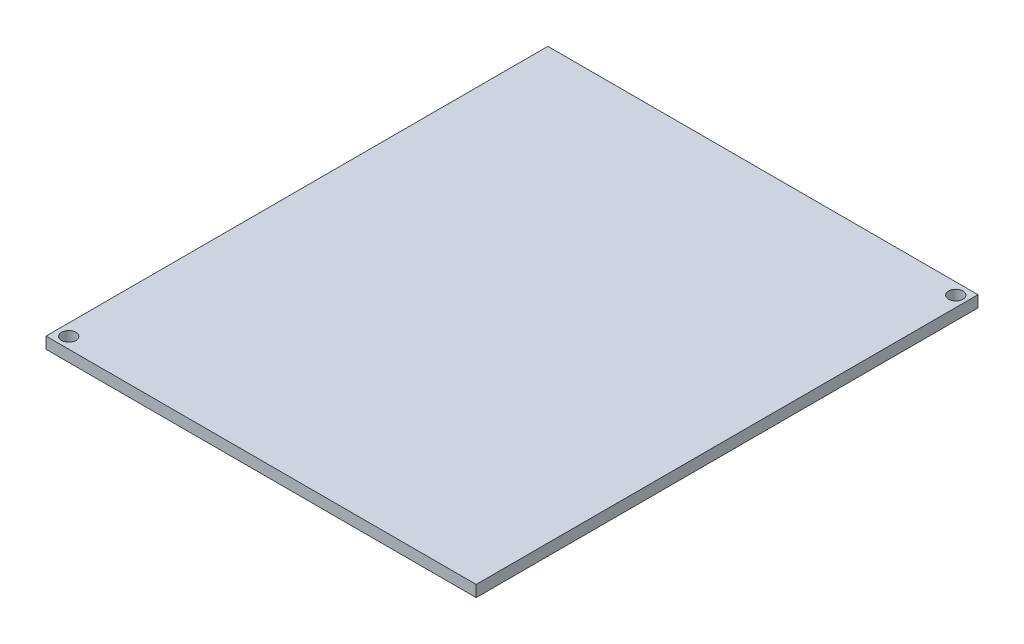
SolidWorks part; units mm, degrees
ref_plane "Přední rovina" through (0, 0, 0) normal (0, 0, 1) x (1, 0, 0)
ref_plane "Horní rovina" through (0, 0, 0) normal (0, 1, 0) x (1, 0, 0)
ref_plane "Pravá rovina" through (0, 0, 0) normal (1, 0, 0) x (0, 0, -1)
sketch "Sketch1" plane through (0, 0, 0) normal (0, 1, 0) x (1, 0, 0)
  line L0 (4105.0112, -3139.6182) -> (4165.0112, -3139.6182) construction
  line L1 (4105.0112, -3138.0182) -> (4165.0112, -3138.0182)
  line L2 (4105.0112, -3138.0182) -> (4105.0112, -3208.0182)
  line L3 (4105.0112, -3208.0182) -> (4165.0112, -3208.0182)
  line L4 (4165.0112, -3138.0182) -> (4165.0112, -3208.0182)
  line L5 (4106.6312, -3138.0182) -> (4106.6312, -3208.0182) construction
  line L6 (4105.0112, -3206.4682) -> (4165.0112, -3206.4682) construction
  line L7 (4163.5112, -3138.0182) -> (4163.5112, -3208.0182) construction
  circle A0 centre (4163.5112, -3139.6182) radius 1
  circle A1 centre (4106.6312, -3206.4682) radius 1
  dimension "D3" = 2
  dimension "D6" = 2
  dimension "D1" = 1.5
  dimension "D2" = 1.6
  dimension "D4" = 1.55
  dimension "D5" = 1.62
  dimension "D7" = 60
  dimension "D8" = 70
extrude "Boss-Extrude1" add sketch "Sketch1" along normal blind 1.6
